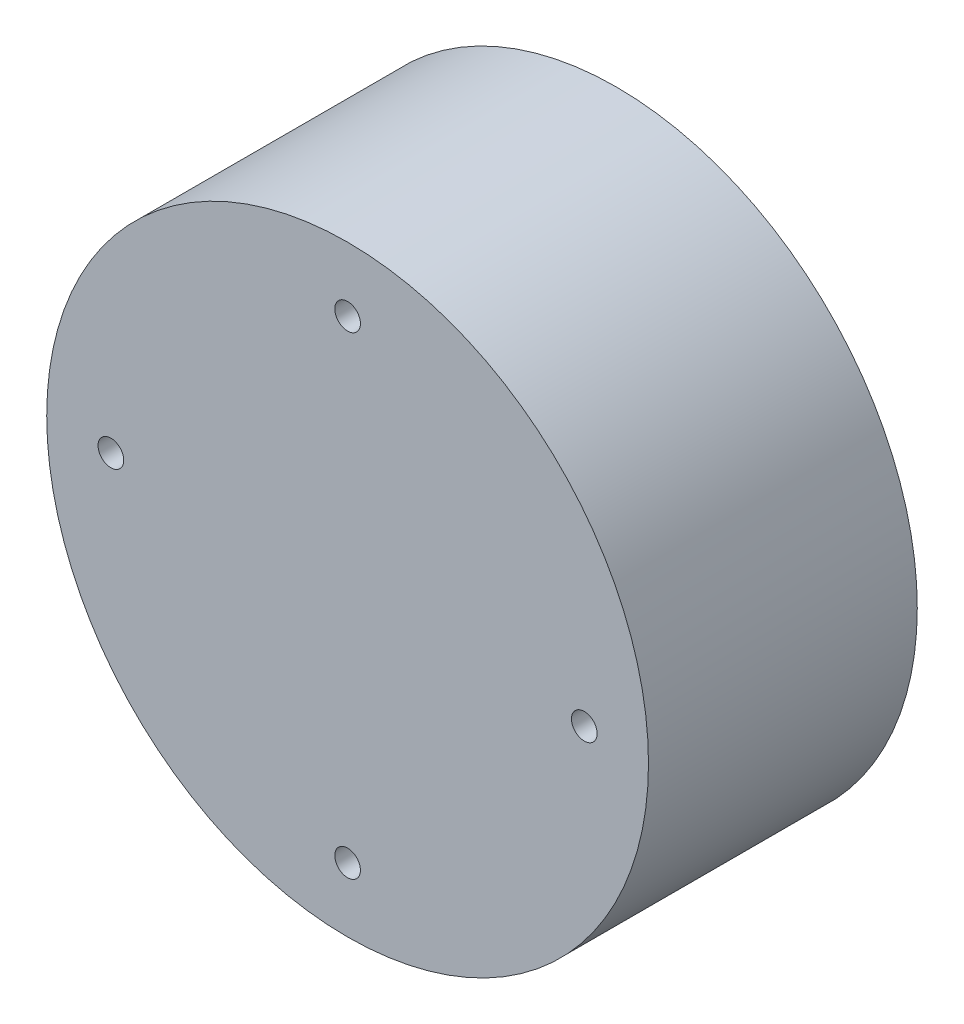
SolidWorks part; units mm, degrees
ref_plane "Plan de face" through (0, 0, 0) normal (0, 0, 1) x (1, 0, 0)
ref_plane "Plan de dessus" through (0, 0, 0) normal (0, 1, 0) x (1, 0, 0)
ref_plane "Plan de droite" through (0, 0, 0) normal (1, 0, 0) x (0, 0, -1)
sketch "Esquisse1" plane through (0, 0, 0) normal (0, 0, 1) x (1, 0, 0)
  circle A0 centre (0, 0) radius 37.5
  dimension "D1" = 75
extrude "Boss.-Extru.1" add sketch "Esquisse1" along normal blind 33.5
sketch "Esquisse2" plane through (0, 0, 33.5) normal (0, 0, 1) x (1, 0, 0)
  line L0 (-37.5, 0) -> (37.5, 0) construction
  line L1 (0, 44.7296) -> (0, -44.9974) construction
  circle A0 centre (0, 0) radius 37.5 construction
  circle A1 centre (0, 29.5) radius 1.6
  circle A2 centre (29.499, 0) radius 1.6
  circle A3 centre (-29.501, 0) radius 1.6
  circle A4 centre (0, -29.5) radius 1.6
  point P2 (0, 0)
  point P5 (0, 0)
  point P18 (-2.5254, -28.4043)
  dimension "D1" = 59
  dimension "D5" = 3.2
  dimension "D6" = 3.2
  dimension "D7" = 3.2
  dimension "D8" = 3.2
  dimension "D2" = 41.72
  dimension "D3" = 41.72
  dimension "D4" = 59
extrude "Enlèv. mat.-Extru.1" cut sketch "Esquisse2" against normal through all
